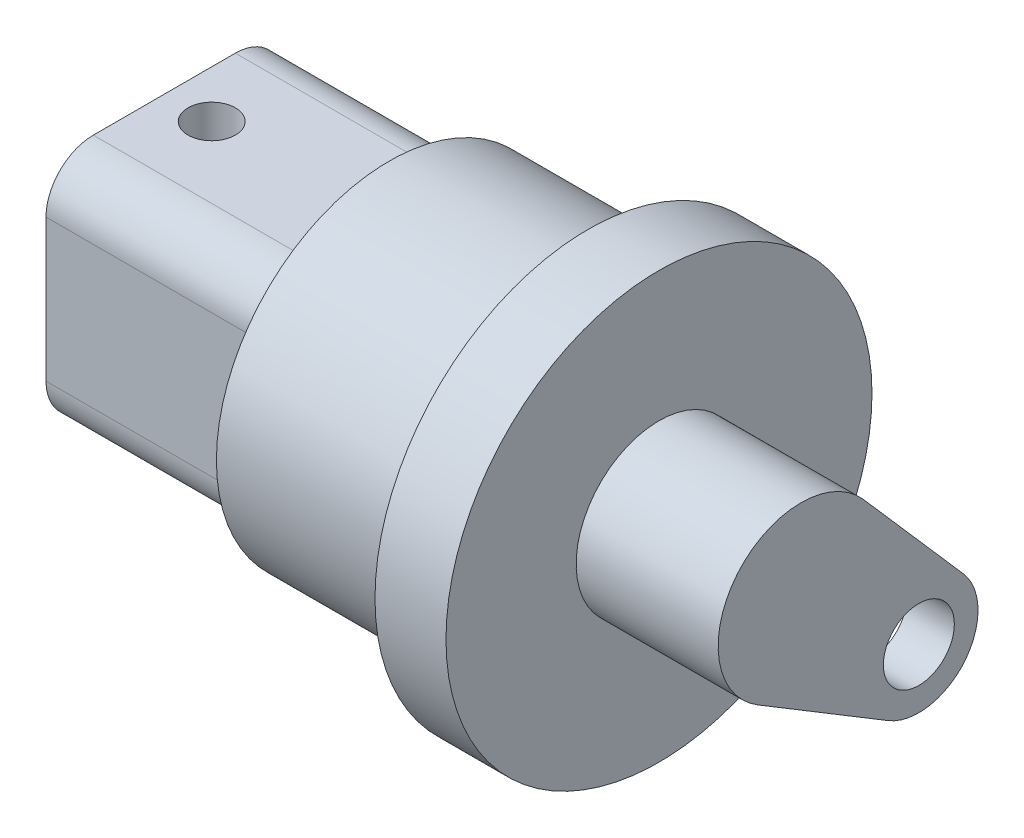
SolidWorks part; units mm, degrees
ref_plane "Front Plane" through (0, 0, 0) normal (0, 0, 1) x (1, 0, 0)
ref_plane "Top Plane" through (0, 0, 0) normal (0, 1, 0) x (1, 0, 0)
ref_plane "Right Plane" through (0, 0, 0) normal (1, 0, 0) x (0, 0, -1)
sketch "Sketch2" plane through (0, 0, 0) normal (1, 0, 0) x (0, 0, -1)
  line L1 (-5, 5) -> (5, 5)
  line L2 (-5, 5) -> (-5, -5)
  line L3 (-5, -5) -> (5, -5)
  line L4 (5, 5) -> (5, -5)
  line L5 (-5, 5) -> (5, -5) construction
  line L6 (-5, -5) -> (5, 5) construction
  circle A0 centre (0, 0) radius 7.3
  circle A1 centre (0, 0) radius 9
  dimension "D1" = 14.6
  dimension "D4" = 18
  dimension "D2" = 10
  dimension "D3" = 10
extrude "Boss-Extrude1" add sketch "Sketch2" along normal blind 3 contours A1
extrude "Boss-Extrude2" add sketch "Sketch2<4>" against normal blind 8.4 contours A0
sketch "Sketch2<4>" plane through (0, 0, 0) normal (1, 0, 0) x (0, 0, -1) same geometry as "Sketch2"
extrude "Boss-Extrude3" add sketch "Sketch2<6>" against normal blind 9.5 from surface contours L4 L3 L2 L1 starting at face at (-8.4, 0, -7.3)
sketch "Sketch2<6>" plane through (0, 0, 0) normal (1, 0, 0) x (0, 0, -1) same geometry as "Sketch2"
sketch "Sketch6" plane through (0, 0, 0) normal (1, 0, 0) x (0, 0, -1)
  line L0 (-5, -5) -> (5, 5) construction
  line L1 (0, 0) -> (8.6111, -7.2256) construction
  line L2 (2.6355, 2.3031) -> (6.8618, -2.533)
  line L4 (-1.8105, -2.9954) -> (3.6861, -6.3177)
  line L5 (0, 0) -> (0, -13.1884) construction
  circle A0 centre (4.9793, -4.1781) radius 2.5
  circle A1 centre (0, 0) radius 9
  circle A2 centre (0, 0) radius 9 construction
  circle A3 centre (0, 0) radius 3.5
  circle A4 centre (4.9793, -4.1781) radius 1.5
  dimension "D2" = 5
  dimension "D3" = 7
  dimension "D4" = 3
  dimension "D1" = 50
extrude "Boss-Extrude6" add sketch "Sketch6" along normal blind 4 from surface contours A3 starting at face at (3, 0, -9)
extrude "Boss-Extrude7" add sketch "Sketch6<4>" along normal blind 2 from surface contours A3 L4 A0 L2 | A3 | A0 A4 region at (0, -2.4234, -2.8881) region at (0, 0, 0) region at (0, -3.3244, -7.2536) starting at face at (7, 0, -3.5)
sketch "Sketch6<4>" plane through (0, 0, 0) normal (1, 0, 0) x (0, 0, -1) same geometry as "Sketch6"
extrude "Cut-Extrude1" cut sketch "Sketch6<5>" against normal up to surface from surface contours A4 L1 | L1 A4 region at (0, -4.1781, -4.9793) up to face at (0, 0, -7.3) starting at face at (3, 0, -3.5)
sketch "Sketch6<5>" plane through (0, 0, 0) normal (1, 0, 0) x (0, 0, -1) same geometry as "Sketch6"
fillet "Fillet1" radius 2 4 edges at (-13.15, 5, 5) (-13.15, -5, 5) (-13.15, -5, -5) (-13.15, 5, -5)
sketch "Sketch7" plane through (0, 0, 0) normal (0, 1, 0) x (1, 0, 0)
  line L0 (-17.9, -3) -> (-17.9, 3) construction
  circle A0 centre (-15.9, 0) radius 1
  dimension "D1" = 2
  dimension "D2" = 2
extrude "Cut-Extrude2" cut sketch "Sketch7" against normal through all both and the other way through all
